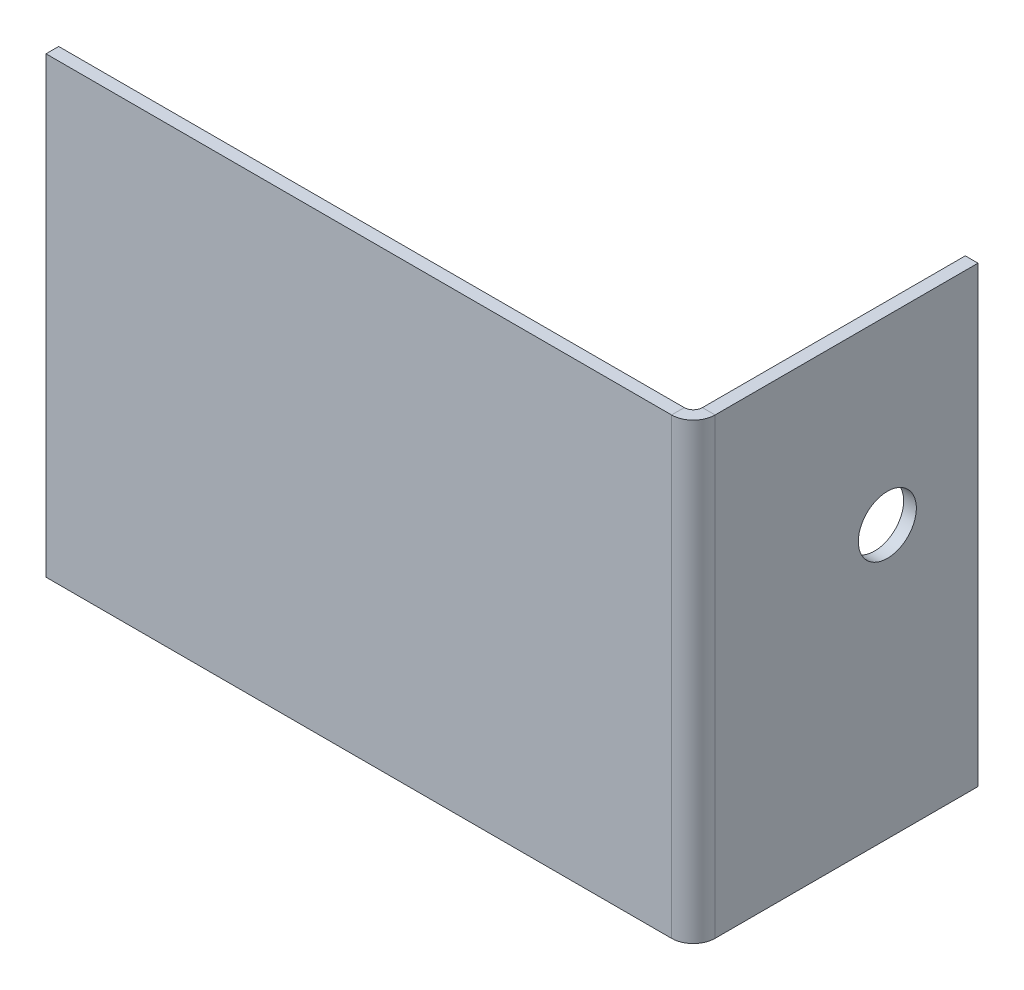
SolidWorks part; units mm, degrees
note: The reader was unsure of these and kept them because the rebuilt part matched: flange length of "Edge-Flange1".
ref_plane "Front Plane" through (0, 0, 0) normal (0, 0, 1) x (1, 0, 0)
ref_plane "Top Plane" through (0, 0, 0) normal (0, 1, 0) x (1, 0, 0)
ref_plane "Right Plane" through (0, 0, 0) normal (1, 0, 0) x (0, 0, -1)
sketch "Sketch1" plane through (0, 0, 0) normal (0, 0, 1) x (1, 0, 0)
  line L1 (-17.5, 12.5) -> (17.5, 12.5)
  line L2 (-17.5, 12.5) -> (-17.5, -12.5)
  line L3 (-17.5, -12.5) -> (17.5, -12.5)
  line L4 (17.5, 12.5) -> (17.5, -12.5)
  line L5 (-17.5, 12.5) -> (17.5, -12.5) construction
  line L6 (-17.5, -12.5) -> (17.5, 12.5) construction
  point P0 (0, 0)
  dimension "D1" = 35
  dimension "D2" = 25
base flange "Base-Flange1" sketch "Sketch1" thickness 0.7 reverse thickness direction no parameters "D1"=0.5
sketch "Sketch6" plane through (0, -12.5, 0) normal (0, 1, 0) x (1, 0, 0)
  line L2 (-17.5, 0.7) -> (17.5, 0.7) construction
  circle A0 centre (16, 2.2) radius 1.5
  dimension "D1" = 3
  dimension "D2" = 1.5
extrude "Boss-Extrude1" [suppressed] add sketch "Sketch6" along normal blind 90 separate body
edge flange "Edge-Flange1" sketch "Sketch9" flange angle 90 flange length 15 flange position material outside bend radius 0.5 thickness 0.7 relief rectangular parameters "D6"=10
sketch "Sketch9" plane through (17.5, 0, -0.7) normal (1, 0, 0) x (0, -1, 0)
  line L2 (-12.5, 0) -> (-12.5, 15)
  line L3 (-12.5, 15) -> (12.5, 15)
  line L4 (12.5, 15) -> (12.5, 0)
  line L7 (12.5, 0) -> (-12.5, 0) construction
  line L8 (12.5, 0) -> (-12.5, 0)
bend "EdgeBend1" bend radius 0.5 bend angle 90 parameters "D5"=1
sketch "Sketch10" plane through (17.5, 0, 0) normal (-1, 0, 0) x (0, 0, 1)
  line L0 (-10.7, 12.6538) -> (-10.7, -12.5) construction
  line L1 (-1.2, -12.5) -> (-15.7, -12.5) construction
  line L2 (-0.7, 12.5) -> (-0.7, -12.5) construction
  circle A0 centre (-10.7, 2.5) radius 1.6
  dimension "D3" = 3.2
  dimension "D1" = 10
  dimension "D2" = 15
extrude "Cut-Extrude1" cut sketch "Sketch10" against normal up to surface (0.7 mm away) up to face at (18.2, 0, -8.45)
sketch "Bend-Lines1" [suppressed] plane through (0, 0, 0) normal (0, 1, 0) x (1, 0, 0)
sketch "Bounding-Box1" [suppressed] plane through (0, 0, 0) normal (0, 1, 0) x (1, 0, 0)
sheet metal parameters "Sheet-Metal1" thickness 0.7 parameters "D1"=0.5
flat pattern "Flat-Pattern1" [suppressed]
sketch "Bend-Lines2" plane through (0, 0, 0) normal (0, 1, 0) x (1, 0, 0)
sketch3d "Bounding-Box2" [suppressed]
  line L0 (15, -12.5, 0) -> (-15, -12.5, 0) construction
  line L1 (15, 12.5, 0) -> (-15, 12.5, 0) construction
  line L2 (15, -12.5, 0) -> (15, 12.5, 0) construction
  line L3 (-15, -12.5, 0) -> (-15, 12.5, 0) construction
sheet metal parameters "Sheet-Metal3" thickness 0.7 parameters "D1"=0.5
flat pattern "Flat-Pattern1" [suppressed]
sketch "Bend-Lines2" plane through (0, 0, 0) normal (0, 0, 1) x (1, 0, 0)
  line L0 (15.1676, -12.5) -> (15.1676, 12.5) construction
  line L1 (15.1676, -12.5) -> (15.1676, 12.5) construction
sketch3d "Bounding-Box2" [suppressed]
  line L0 (-15, -12.5, 0) -> (30.3352, -12.5, 0) construction
  line L1 (-15, 12.5, 0) -> (30.3352, 12.5, 0) construction
  line L2 (-15, -12.5, 0) -> (-15, 12.5, 0) construction
  line L3 (30.3352, -12.5, 0) -> (30.3352, 12.5, 0) construction
bend of the flat pattern "Flatten-<EdgeBend1>1"
sketch "Sketch10-1" [suppressed] plane through (14.6352, 0, -0.7) normal (0, 0, -1) x (-1, 0, 0)
  line L0 (-10.7, 12.6538) -> (-10.7, -12.5) construction
  line L2 (29.6352, 12.5) -> (29.6352, -12.5)
  circle A0 centre (-10.7, 2.5) radius 1.696
  dimension "D1" = 40.3352
  dimension "D2" = 15
sheet metal parameters "Sheet-Metal4" thickness 0.7 parameters "D1"=0.5
flat pattern "Flat-Pattern1" [suppressed]
sketch "Bend-Lines2" plane through (0, 0, 0) normal (0, 0, 1) x (1, 0, 0)
  line L0 (17.6676, -12.5) -> (17.6676, 12.5) construction
  line L1 (17.6676, -12.5) -> (17.6676, 12.5) construction
sketch3d "Bounding-Box2" [suppressed]
  line L0 (-17.5, -12.5, 0) -> (32.8352, -12.5, 0) construction
  line L1 (-17.5, 12.5, 0) -> (32.8352, 12.5, 0) construction
  line L2 (-17.5, -12.5, 0) -> (-17.5, 12.5, 0) construction
  line L3 (32.8352, -12.5, 0) -> (32.8352, 12.5, 0) construction
bend of the flat pattern "Flatten-<EdgeBend1>1"
sketch "Sketch10-1" plane through (17.1352, 0, -0.7) normal (0, 0, -1) x (-1, 0, 0)
  line L0 (-10.7, 12.6538) -> (-10.7, -12.5) construction
  line L2 (34.6352, 12.5) -> (34.6352, -12.5) construction
  circle A0 centre (-10.7, 2.5) radius 1.6
  dimension "D3" = 3.2
  dimension "D1" = 45.3352
  dimension "D2" = 15
